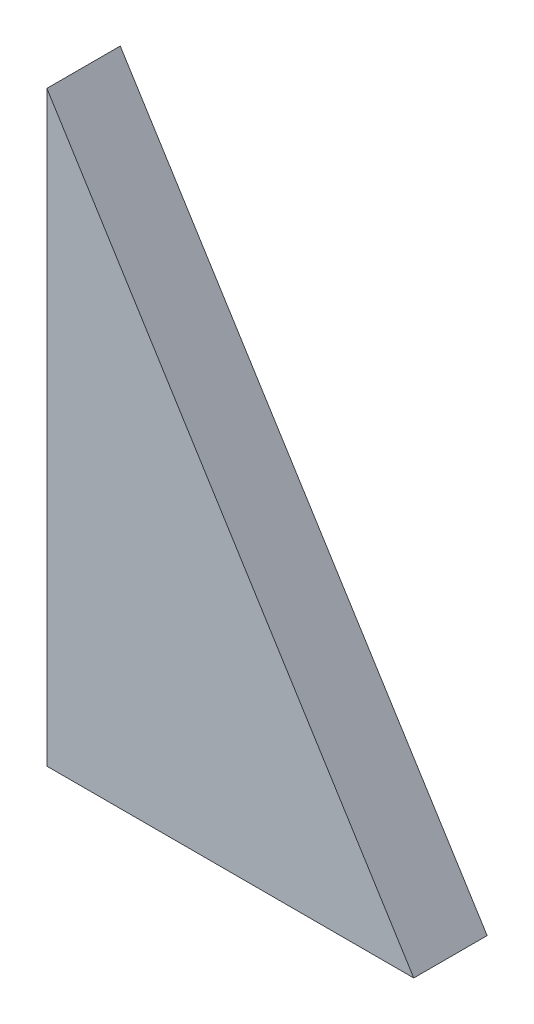
SolidWorks part; units mm, degrees
ref_plane "Front Plane" through (0, 0, 0) normal (0, 0, 1) x (1, 0, 0)
ref_plane "Top Plane" through (0, 0, 0) normal (0, 1, 0) x (1, 0, 0)
ref_plane "Right Plane" through (0, 0, 0) normal (1, 0, 0) x (0, 0, -1)
sketch "Sketch1" plane through (0, 0, 0) normal (0, 0, 1) x (1, 0, 0)
  line L1 (-15.875, -25.4) -> (15.875, -25.4)
  line L2 (-15.875, -25.4) -> (-15.875, 25.4)
  line L3 (-15.875, 25.4) -> (15.875, 25.4)
  line L4 (15.875, -25.4) -> (15.875, 25.4)
  line L5 (-15.875, -25.4) -> (15.875, 25.4) construction
  line L6 (-15.875, 25.4) -> (15.875, -25.4) construction
  point P0 (0, 0)
  dimension "D1" = 31.75
  dimension "D2" = 50.8
extrude "Boss-Extrude1" add sketch "Sketch1" along normal blind 6.35
sketch "Sketch3" plane through (0, 0, 6.35) normal (0, 0, 1) x (1, 0, 0)
  line L0 (-15.875, 25.4) -> (15.875, -25.4)
extrude "Cut-Extrude1" cut sketch "Sketch3" along normal through all and the other way through all
